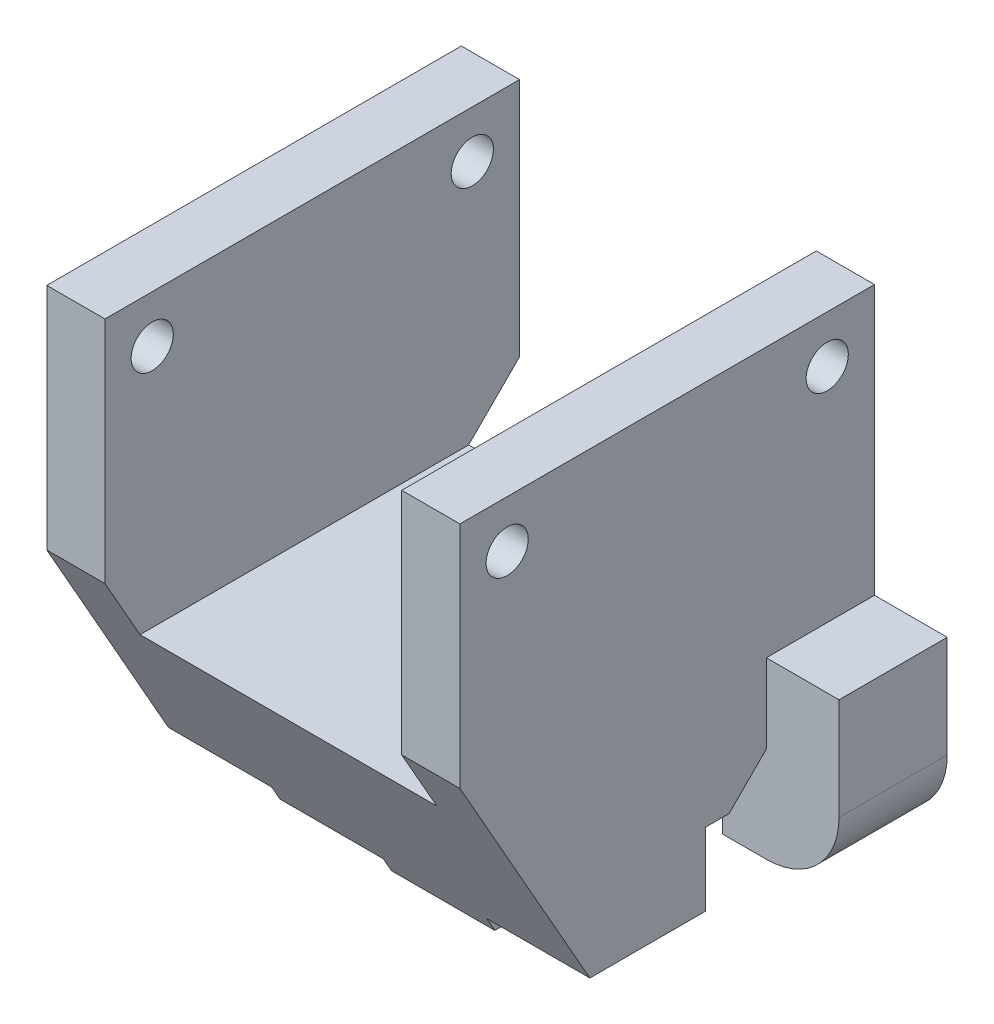
SolidWorks part; units mm, degrees
ref_plane "Front Plane" through (0, 0, 0) normal (0, 0, 1) x (1, 0, 0)
ref_plane "Top Plane" through (0, 0, 0) normal (0, 1, 0) x (1, 0, 0)
ref_plane "Right Plane" through (0, 0, 0) normal (1, 0, 0) x (0, 0, -1)
sketch "Sketch1" plane through (0, 0, 0) normal (0, 0, 1) x (1, 0, 0)
  line L1 (-17, 23.25) -> (17, 23.25)
  line L2 (-17, 23.25) -> (-17, -23.25)
  line L3 (-17, -23.25) -> (17, -23.25)
  line L4 (17, 23.25) -> (17, -23.25)
  line L5 (-17, 23.25) -> (17, -23.25) construction
  line L6 (-17, -23.25) -> (17, 23.25) construction
  point P0 (0, 0)
  dimension "D1" = 34
  dimension "D2" = 46.5
extrude "Boss-Extrude1" add sketch "Sketch1" along normal blind 28.5
sketch "Sketch2" plane through (17, 0, 0) normal (1, 0, 0) x (0, 0, -1)
  line L0 (-28.5, -23.25) -> (-28.5, 23.25) construction
  line L1 (-28.5, 23.25) -> (0, 23.25) construction
  circle A0 centre (-25.25, 20) radius 1.45
  circle A1 centre (-3.25, 20) radius 1.45
  circle A2 centre (-3.25, -20) radius 1.45
  circle A3 centre (-25.25, -20) radius 1.45
  dimension "D1" = 2.9
  dimension "D2" = 3.25
  dimension "D3" = 3.25
  dimension "D4" = 2
  dimension "D5" = 2
extrude "Cut-Extrude1" cut sketch "Sketch2" against normal through all
sketch "Sketch3" plane through (17, 0, 0) normal (1, 0, 0) x (0, 0, -1)
  line L0 (0, -23.25) -> (0, 23.25) construction
  line L1 (-28.5, -23.25) -> (0, -23.25)
  line L2 (-28.5, -23.25) -> (-28.5, -3.25)
  line L3 (-28.5, -3.25) -> (0, -3.25)
  line L4 (0, -23.25) -> (0, -3.25)
  dimension "D1" = 20
extrude "Cut-Extrude2" cut sketch "Sketch3" against normal through all
sketch "Sketch4" plane through (0, 0, 0) normal (0, 0, -1) x (-1, 0, 0)
  line L0 (-17, 23.25) -> (17, 23.25) construction
  line L1 (-13, 23.25) -> (13, 23.25)
  line L2 (-13, 23.25) -> (-13, 3.25)
  line L3 (-13, 3.25) -> (13, 3.25)
  line L4 (13, 23.25) -> (13, 3.25)
  line L5 (-17, -3.25) -> (-17, 23.25) construction
  line L6 (17, 23.25) -> (17, -3.25) construction
  dimension "D1" = 4
  dimension "D2" = 4
  dimension "D3" = 20
extrude "Cut-Extrude3" cut sketch "Sketch4" against normal through all
sketch "Sketch5" plane through (17, 0, 0) normal (1, 0, 0) x (0, 0, -1)
  line L0 (0, -3.25) -> (-28.5, -3.25) construction
  line L1 (-7.4371, 4.75) -> (0, 4.75)
  line L2 (-7.4371, 4.75) -> (-7.4371, -10.25)
  line L3 (-7.4371, -10.25) -> (0, -10.25)
  line L4 (0, 4.75) -> (0, -10.25)
  dimension "D1" = 8
  dimension "D2" = 15
extrude "Boss-Extrude2" add sketch "Sketch5" along normal blind 5 and the other way blind 3
sketch "Sketch6" plane through (-13, 0, 0) normal (1, 0, 0) x (0, 0, -1)
  line L1 (-28.5, 23.25) -> (0, 23.25)
  line L2 (-28.5, 23.25) -> (-28.5, 3.25)
  line L3 (-28.5, 3.25) -> (0, 3.25)
  line L4 (0, 23.25) -> (0, 3.25)
  circle A0 centre (-25.25, 20) radius 1.45
  circle A1 centre (-3.25, 20) radius 1.45
extrude "Boss-Extrude3" add sketch "Sketch6" along normal blind 5.6
sketch "Sketch7" plane through (0, 0, 0) normal (0, 0, -1) x (-1, 0, 0)
  line L0 (17, -3.25) -> (-14, -3.25) construction
  line L1 (17, 23.25) -> (11.4, 23.25)
  line L2 (17, 23.25) -> (17, -3.25)
  line L3 (17, -3.25) -> (11.4, -3.25)
  line L4 (11.4, 23.25) -> (11.4, -3.25)
  dimension "D1" = 5.6
extrude "Cut-Extrude4" cut sketch "Sketch7" against normal through all
sketch "Sketch9" plane through (0, -3.25, 0) normal (0, -1, 0) x (1, 0, 0)
  line L1 (-11.4, 28.5) -> (-4.3, 28.5)
  line L2 (-11.4, 28.5) -> (-11.4, 14.5)
  line L3 (-11.4, 14.5) -> (-4.3, 14.5)
  line L4 (-4.3, 28.5) -> (-4.3, 14.5)
  line L5 (-4.3, 28.5) -> (2.8, 28.5)
  line L6 (-4.3, 28.5) -> (-4.3, 11.5)
  line L7 (-4.3, 11.5) -> (2.8, 11.5)
  line L8 (2.8, 28.5) -> (2.8, 11.5)
  line L9 (2.8, 28.5) -> (9.9, 28.5)
  line L10 (2.8, 28.5) -> (2.8, 9.5)
  line L11 (2.8, 9.5) -> (9.9, 9.5)
  line L12 (9.9, 28.5) -> (9.9, 9.5)
  line L13 (17, 28.5) -> (9.9, 28.5)
  line L14 (17, 28.5) -> (17, 11.6031)
  line L15 (17, 11.6031) -> (9.9, 11.6031)
  line L16 (9.9, 28.5) -> (9.9, 11.6031)
  line M6 (17, 28.5) -> (-11.4, 28.5)
  line M7 (-11.4, 28.5) -> (-11.4, 0)
  line M11 (17, 7.4371) -> (17, 28.5)
  dimension "D1" = 7.1
  dimension "D2" = 7.1
  dimension "D3" = 7.1
  dimension "D4" = 14
  dimension "D5" = 3
  dimension "D6" = 2
extrude "Boss-Extrude4" add sketch "Sketch9" along normal blind 4 contours L4 L3 M6 M7 | L8 L4 L6 L7 M6 | L15 L12 M11 M6 | L12 L8 L10 L11 M6 region at (-7.85, -3.25, 21.5) region at (-0.75, -3.25, 20) region at (6.35, -3.25, 19) region at (13.45, -3.25, 20.0516)
sketch "Sketch10" plane through (0, -7.25, 0) normal (0, -1, 0) x (1, 0, 0)
  line L0 (17, 28.5) -> (-11.4, 28.5) construction
  line L1 (-4.3, 11.5) -> (2.8, 11.5)
  line L2 (-4.3, 11.5) -> (-4.3, 28.5)
  line L3 (-4.3, 28.5) -> (2.8, 28.5)
  line L4 (2.8, 11.5) -> (2.8, 28.5)
extrude "Boss-Extrude5" add sketch "Sketch10" along normal blind 1
sketch "Sketch11" plane through (0, -7.25, 0) normal (0, -1, 0) x (1, 0, 0)
  line L1 (9.9, 9.5) -> (2.8, 9.5)
  line L2 (9.9, 9.5) -> (9.9, 28.5)
  line L3 (9.9, 28.5) -> (2.8, 28.5)
  line L4 (2.8, 9.5) -> (2.8, 28.5)
extrude "Boss-Extrude6" add sketch "Sketch11" along normal blind 2
sketch "Sketch12" plane through (0, -7.25, 0) normal (0, -1, 0) x (1, 0, 0)
  line L1 (9.9, 28.5) -> (17, 28.5)
  line L2 (9.9, 28.5) -> (9.9, 11.6031)
  line L3 (9.9, 11.6031) -> (17, 11.6031)
  line L4 (17, 28.5) -> (17, 11.6031)
extrude "Boss-Extrude7" add sketch "Sketch12" along normal blind 1
sketch "Sketch13" plane through (17, 0, 0) normal (1, 0, 0) x (0, 0, -1)
  line L0 (-19, -9.25) -> (-28.5, 7.5)
  line L1 (-9.5, -9.25) -> (-28.5, -9.25) construction
  line L2 (-28.5, -8.25) -> (-28.5, 23.25) construction
  line L3 (-28.5, 7.5) -> (-28.5, -9.25)
  line L4 (-28.5, -9.25) -> (-19, -9.25)
  line L5 (0, -10.25) -> (0, 4.75) construction
  line L6 (-7.4371, -10.25) -> (0, -10.25)
  line L7 (-7.4371, -10.25) -> (-7.4371, -7.25)
  line L8 (-7.4371, -7.25) -> (0, -7.25)
  line L9 (0, -10.25) -> (0, -7.25)
  dimension "D1" = 3
extrude "Cut-Extrude5" cut sketch "Sketch13" against normal through all and the other way through all
ref_plane "Plane1" through (32, 0, 0) normal (1, 0, 0) x (0, 0, -1)
fillet "Fillet1" radius 5 1 edges at (22, -7.25, 3.7185)
chamfer "Chamfer1" distance 10 angle 45 1 edges at (1.3, -3.25, 0)
